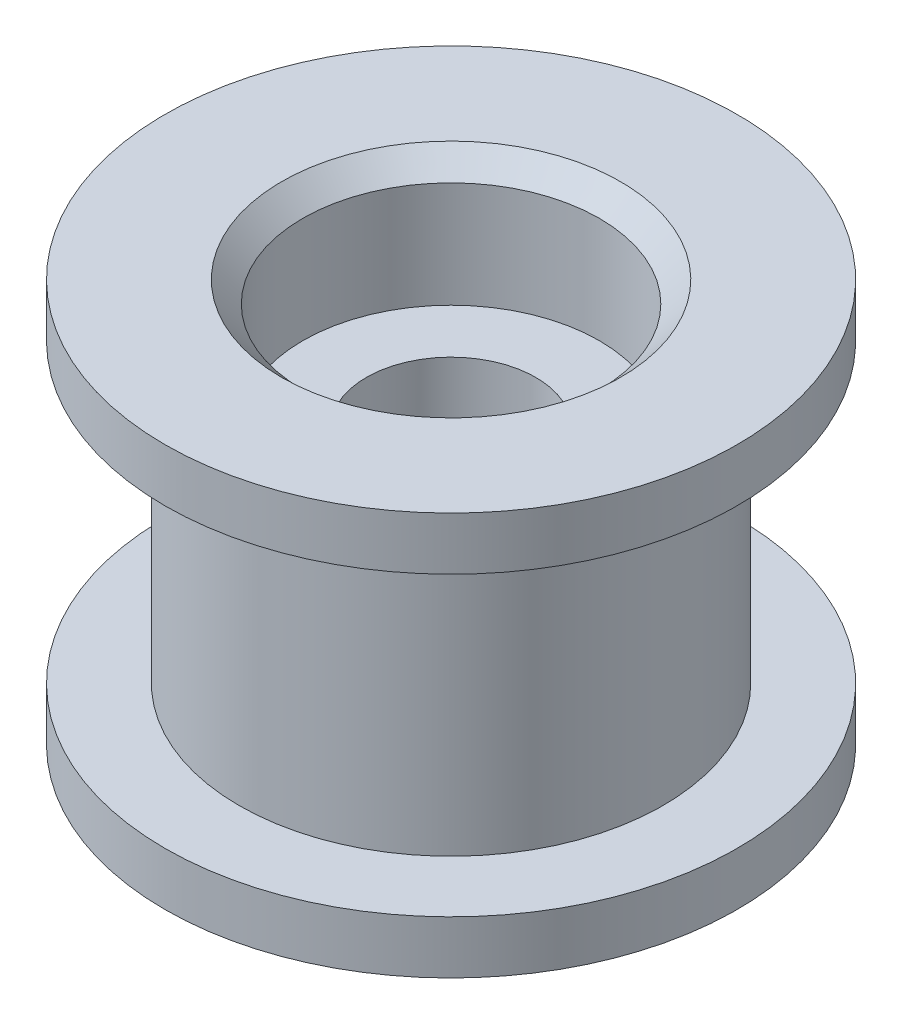
SolidWorks part; units mm, degrees
ref_plane "Front" through (0, 0, 0) normal (0, 0, 1) x (1, 0, 0)
ref_plane "Top" through (0, 0, 0) normal (0, 1, 0) x (1, 0, 0)
ref_plane "Right" through (0, 0, 0) normal (1, 0, 0) x (0, 0, -1)
sketch "Sketch2" plane through (0, 0, 0) normal (0, 1, 0) x (1, 0, 0)
  circle A0 centre (0, 0) radius 5
  dimension "D1" = 10
extrude "Boss-Extrude1" add sketch "Sketch2" along normal blind 7
sketch "Sketch3" plane through (0, 7, 0) normal (0, 1, 0) x (1, 0, 0)
  circle A0 centre (0, 0) radius 6.75
  dimension "D1" = 13.5
extrude "Boss-Extrude2" add sketch "Sketch3" along normal blind 1.25
extrude "Boss-Extrude3" add sketch "Sketch3<2>" against normal blind 1.25 from surface starting at face at (0, 0, 5)
sketch "Sketch3<2>" plane through (0, 7, 0) normal (0, 1, 0) x (1, 0, 0) same geometry as "Sketch3"
sketch "Sketch4" plane through (0, -1.25, 0) normal (0, -1, 0) x (1, 0, 0)
  circle A0 centre (0, 0) radius 3.5
  dimension "D1" = 7
extrude "Cut-Extrude1" cut sketch "Sketch4" against normal blind 3
sketch "Sketch5" plane through (0, 8.25, 0) normal (0, 1, 0) x (1, 0, 0)
  circle A0 centre (0, 0) radius 3.5
  dimension "D1" = 7
extrude "Cut-Extrude2" cut sketch "Sketch5" against normal blind 3
sketch "Sketch6" plane through (0, 5.25, 0) normal (0, 1, 0) x (1, 0, 0)
  circle A0 centre (0, 0) radius 2
  dimension "D1" = 4
extrude "Cut-Extrude3" cut sketch "Sketch6" against normal through all
chamfer "Chamfer1" distance 0.5 angle 45 2 edges at (0, 8.25, 3.5) (0, -1.25, -3.5)
